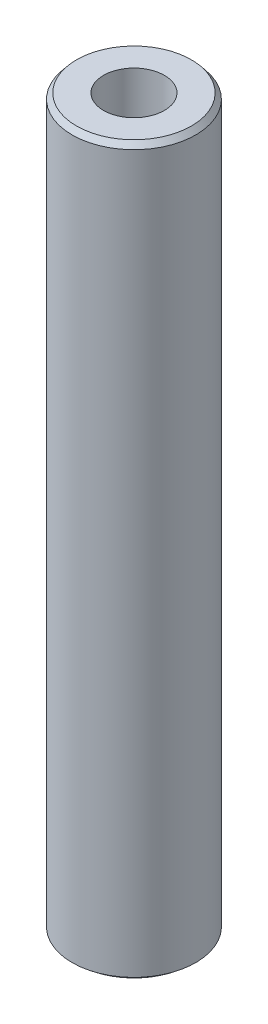
SolidWorks part; units mm, degrees
ref_plane "Front Plane" through (0, 0, 0) normal (0, 0, 1) x (1, 0, 0)
ref_plane "Top Plane" through (0, 0, 0) normal (0, 1, 0) x (1, 0, 0)
ref_plane "Right Plane" through (0, 0, 0) normal (1, 0, 0) x (0, 0, -1)
sketch "Sketch1" plane through (0, 0, 0) normal (0, 1, 0) x (1, 0, 0)
  circle A0 centre (0, 0) radius 15
  dimension "SHAFT_OD" = 30
extrude "Boss-Extrude1" add sketch "Sketch1" along normal blind 176.2419
sketch "Sketch2" plane through (0, 0, 0) normal (0, 1, 0) x (1, 0, 0)
  circle A0 centre (0, 0) radius 7.3831
  dimension "BORE_D" = 14.7661
extrude "Cut-Extrude1" cut sketch "Sketch2" along normal through all
chamfer "Chamfer1" distance 1.3303 angle 38.861 2 edges at (0, 176.2419, 15) (0, 0, 15) first distance on face at (0, 176.2419, 15) first distance on face at (0, 0, 7.3831)
